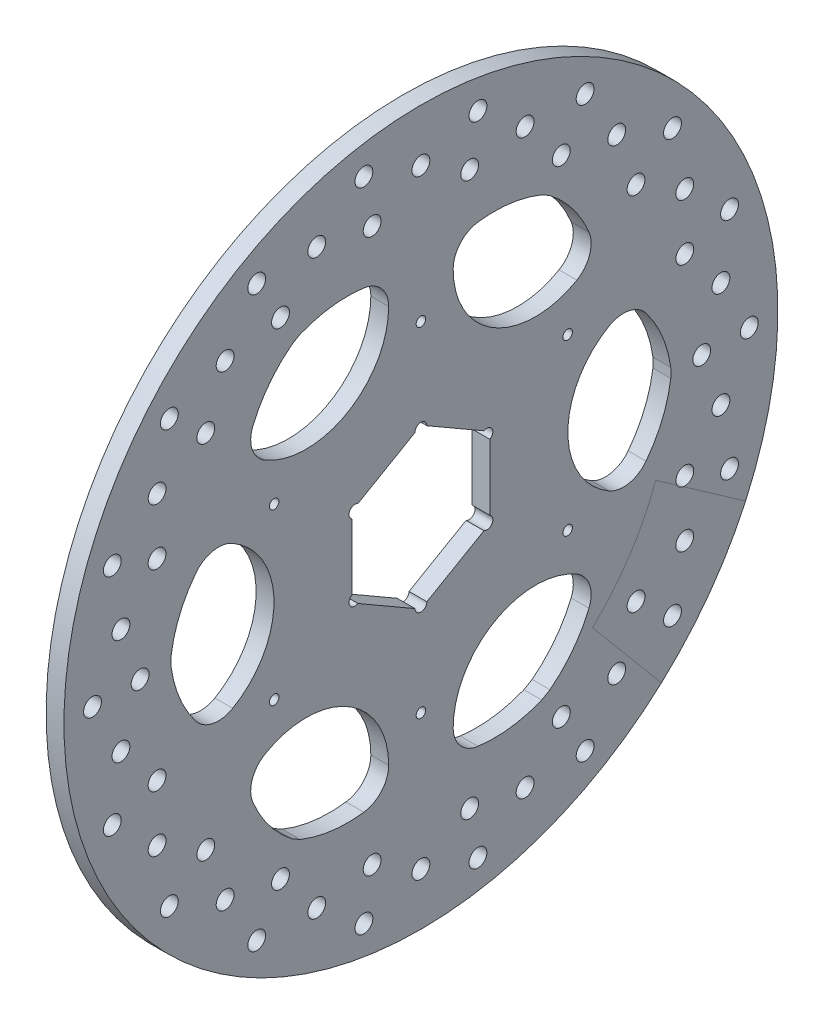
SolidWorks part; units mm, degrees
material "Gray Cast Iron (w/YS)"
ref_plane "X-Y Datum" through (0, 0, 0) normal (0, 0, 1) x (1, 0, 0)
ref_plane "X-Z Datum" through (0, 0, 0) normal (0, 1, 0) x (1, 0, 0)
ref_plane "Y-Z Datum" through (0, 0, 0) normal (1, 0, 0) x (0, 0, -1)
sketch "Sketch1" plane through (0, 0, 0) normal (1, 0, 0) x (0, 0, -1)
  circle A0 centre (0, 0) radius 95.25
  circle A1 centre (0, 0) radius 66.675
  dimension "D1" = 190.5
  dimension "D2" = 133.35
extrude "Main Rotor" add sketch "Sketch1" along normal blind 4.7625
sketch "Sketch2" plane through (4.7625, 0, 0) normal (1, 0, 0) x (0, 0, -1)
  line L0 (0, 0) -> (-50000, 0) construction
  line L1 (0, 0) -> (-93.8029, 16.54) construction
  line L4 (-82.3453, 29.9712) -> (-70.4112, 25.6276) construction
  circle A2 centre (0, 0) radius 95.25 construction
  circle A72 centre (-80.0452, 14.1141) radius 2.3813
  circle A73 centre (0, 0) radius 66.675 construction
  circle A74 centre (-82.3453, 29.9712) radius 2.3812
  circle A75 centre (-70.4112, 25.6276) radius 2.3813
  circle A76 centre (0, 0) radius 95.25 construction
  circle A77 centre (-70.3905, 40.64) radius 2.3812
  circle A78 centre (-67.1285, 56.3275) radius 2.3813
  circle A79 centre (0, 0) radius 66.675 construction
  circle A80 centre (-57.3997, 48.1641) radius 2.3813
  circle A81 centre (-52.2458, 62.2641) radius 2.3813
  circle A82 centre (-87.63, 0) radius 2.3813
  circle A83 centre (-43.815, 75.8898) radius 2.3812
  circle A84 centre (-37.465, 64.8913) radius 2.3813
  circle A85 centre (-74.93, 0) radius 2.3813
  circle A86 centre (-27.7994, 76.3782) radius 2.3812
  circle A87 centre (-15.2168, 86.2987) radius 2.3813
  circle A88 centre (-13.0115, 73.7916) radius 2.3813
  circle A89 centre (0, 81.28) radius 2.3813
  circle A90 centre (15.2168, 86.2987) radius 2.3813
  circle A91 centre (13.0115, 73.7916) radius 2.3813
  circle A92 centre (27.7994, 76.3782) radius 2.3813
  circle A93 centre (43.815, 75.8898) radius 2.3813
  circle A94 centre (37.465, 64.8913) radius 2.3813
  circle A95 centre (52.2458, 62.2641) radius 2.3813
  circle A96 centre (67.1285, 56.3275) radius 2.3813
  circle A97 centre (57.3997, 48.1641) radius 2.3813
  circle A98 centre (70.3905, 40.64) radius 2.3812
  circle A99 centre (82.3453, 29.9712) radius 2.3813
  circle A100 centre (70.4112, 25.6276) radius 2.3813
  circle A101 centre (80.0452, 14.1141) radius 2.3813
  circle A102 centre (87.63, 0) radius 2.3813
  circle A103 centre (74.93, 0) radius 2.3813
  circle A104 centre (80.0452, -14.1141) radius 2.3813
  circle A105 centre (82.3453, -29.9712) radius 2.3812
  circle A106 centre (70.4112, -25.6276) radius 2.3812
  circle A107 centre (70.3905, -40.64) radius 2.3813
  circle A108 centre (67.1285, -56.3275) radius 2.3812
  circle A109 centre (57.3997, -48.1641) radius 2.3813
  circle A110 centre (52.2458, -62.2641) radius 2.3812
  circle A111 centre (43.815, -75.8898) radius 2.3813
  circle A112 centre (37.465, -64.8913) radius 2.3813
  circle A113 centre (27.7994, -76.3782) radius 2.3813
  circle A114 centre (15.2168, -86.2987) radius 2.3813
  circle A115 centre (13.0115, -73.7916) radius 2.3812
  circle A116 centre (0, -81.28) radius 2.3812
  circle A117 centre (-15.2168, -86.2987) radius 2.3813
  circle A118 centre (-13.0115, -73.7916) radius 2.3813
  circle A119 centre (-27.7994, -76.3782) radius 2.3812
  circle A120 centre (-43.815, -75.8898) radius 2.3813
  circle A121 centre (-37.465, -64.8913) radius 2.3813
  circle A122 centre (-52.2458, -62.2641) radius 2.3813
  circle A123 centre (-67.1285, -56.3275) radius 2.3813
  circle A124 centre (-57.3997, -48.1641) radius 2.3813
  circle A125 centre (-70.3905, -40.64) radius 2.3813
  circle A126 centre (-82.3453, -29.9712) radius 2.3813
  circle A127 centre (-70.4112, -25.6276) radius 2.3813
  circle A128 centre (-80.0452, -14.1141) radius 2.3813
  point P109 (0, 0)
  dimension "D1" = 4.7625
  dimension "D2" = 12.7
  dimension "D3" = 10
  dimension "D5" = 81.28
  dimension "D4" = 87.63
  dimension "D6" = 18
extrude "Cut Slots" cut sketch "Sketch2" against normal through all
sketch "Sketch3" plane through (4.7625, 0, 0) normal (1, 0, 0) x (0, 0, -1)
  line L0 (0.3454, 5.0869) -> (-47951.5604, 14168.94) construction
  line L1 (0, 21.2491) -> (-18.4023, 10.6246)
  line L2 (-18.4023, 10.6246) -> (-18.4023, -10.6246)
  line L3 (-18.4023, -10.6246) -> (0, -21.2491)
  line L4 (0, -21.2491) -> (18.4023, -10.6246)
  line L5 (18.4023, -10.6246) -> (18.4023, 10.6246)
  line L6 (18.4023, 10.6246) -> (0, 21.2491)
  line L7 (0, 0) -> (43301.2702, 25000) construction
  line L8 (0, 0) -> (0, 50000) construction
  line L12 (9.525, -59.2994) -> (-9.525, -59.2994) construction
  line L17 (-30.6007, -53.002) -> (24969.3838, 43248.2414) construction
  line L18 (-60.783, 0) -> (49939.217, 0) construction
  line L19 (0, 0) -> (-25000, 43301.2702) construction
  line L20 (-14.2015, 9.3837) -> (0, 17.583) construction
  line L21 (-1.5875, 20.3326) -> (-2.825, 22.476) construction
  arc A0 (8.6043, -53.0208) -> (15.2264, -60.5686) centre (16.2243, -53.0143) ccw
  circle A1 centre (0, 0) radius 66.675 construction
  arc A7 (-15.2264, -60.5686) -> (-32.2316, -58.3668) centre (-19.5921, -27.5182) cw
  arc A10 (15.2264, -60.5686) -> (32.2316, -58.3668) centre (19.5921, -27.5182) ccw
  arc A19 (-19.6024, -33.9524) -> (-8.6043, -53.0208) centre (-30.6006, -53.0019) cw
  arc A25 (41.6152, -33.9619) -> (44.8408, -43.4707) centre (37.7996, -40.5577) cw
  arc A26 (34.4313, -57.0968) -> (66.6629, -1.27) centre (0, 0) ccw
  arc A27 (50.2195, -19.0589) -> (60.0672, -17.0979) centre (54.0238, -12.4565) ccw
  arc A28 (19.6024, -33.9524) -> (8.6043, -53.0208) centre (30.6006, -53.0019) ccw
  arc A29 (60.0672, 17.0979) -> (50.2195, 19.0589) centre (54.0238, 12.4565) ccw
  arc A30 (-44.8408, -43.4707) -> (-34.4313, -57.0968) centre (-14.0354, -30.7264) ccw
  arc A31 (-19.6024, -33.9524) -> (-41.6152, -33.9619) centre (-30.6006, -53.0019) ccw
  arc A32 (-39.2049, 0) -> (-50.2195, -19.0589) centre (-61.2013, 0) cw
  arc A33 (-60.0672, -17.0979) -> (-66.6629, -1.27) centre (-33.6275, 3.2082) cw
  arc A34 (-60.0672, 17.0979) -> (-66.6629, 1.27) centre (-33.6275, -3.2082) ccw
  arc A35 (44.8408, 43.4707) -> (41.6152, 33.9619) centre (37.7996, 40.5577) cw
  arc A36 (-32.2316, -58.3668) -> (32.2316, -58.3668) centre (0, 0) ccw
  arc A37 (15.2264, 60.5686) -> (8.6043, 53.0208) centre (16.2243, 53.0143) ccw
  arc A38 (-8.6043, 53.0208) -> (-15.2264, 60.5686) centre (-16.2243, 53.0143) ccw
  arc A39 (-44.8408, 43.4707) -> (-41.6152, 33.9619) centre (-37.7996, 40.5577) ccw
  arc A40 (-50.2195, 19.0589) -> (-60.0672, 17.0979) centre (-54.0238, 12.4565) ccw
  arc A41 (-50.2195, -19.0589) -> (-60.0672, -17.0979) centre (-54.0238, -12.4565) cw
  arc A42 (-8.6043, -53.0208) -> (-15.2264, -60.5686) centre (-16.2243, -53.0143) cw
  arc A43 (-41.6152, -33.9619) -> (-44.8408, -43.4707) centre (-37.7996, -40.5577) ccw
  arc A44 (-39.2049, 0) -> (-50.2195, 19.0589) centre (-61.2013, 0) ccw
  arc A45 (-19.6025, 33.9524) -> (-41.6152, 33.9619) centre (-30.6007, 53.0019) cw
  arc A46 (-44.8408, 43.4707) -> (-34.4313, 57.0968) centre (-14.0354, 30.7264) cw
  arc A47 (-15.2264, 60.5686) -> (-32.2316, 58.3668) centre (-19.5921, 27.5182) ccw
  arc A48 (-19.6025, 33.9524) -> (-8.6043, 53.0208) centre (-30.6007, 53.0019) ccw
  arc A49 (19.6024, 33.9524) -> (8.6043, 53.0208) centre (30.6006, 53.0019) cw
  arc A50 (15.2264, 60.5686) -> (32.2316, 58.3668) centre (19.5921, 27.5182) cw
  arc A51 (44.8408, 43.4707) -> (34.4313, 57.0968) centre (14.0354, 30.7264) ccw
  arc A52 (19.6024, 33.9524) -> (41.6152, 33.9619) centre (30.6006, 53.0019) ccw
  arc A53 (39.2049, 0) -> (50.2195, 19.0589) centre (61.2013, 0) cw
  arc A54 (60.0672, 17.0979) -> (66.6629, 1.27) centre (33.6275, -3.2082) cw
  arc A55 (60.0672, -17.0979) -> (66.6629, -1.27) centre (33.6275, 3.2082) ccw
  arc A56 (39.2049, 0) -> (50.2195, -19.0589) centre (61.2013, 0) ccw
  arc A57 (19.6024, -33.9524) -> (41.6152, -33.9619) centre (30.6007, -53.0019) cw
  arc A58 (44.8408, -43.4707) -> (34.4313, -57.0968) centre (14.0354, -30.7264) cw
  circle A59 centre (0, 20.3326) radius 1.5875
  arc A60 (-66.6629, -1.27) -> (-34.4313, -57.0968) centre (0, 0) ccw
  arc A62 (-34.4313, 57.0968) -> (-66.6629, 1.27) centre (0, 0) ccw
  arc A64 (32.2316, 58.3668) -> (-32.2316, 58.3668) centre (0, 0) ccw
  arc A66 (66.6629, 1.27) -> (34.4313, 57.0968) centre (0, 0) ccw
  circle A71 centre (0, 0) radius 7.4362 construction
  circle A72 centre (0, 17.583) radius 3.175 construction
  circle A73 centre (17.6086, 10.1663) radius 1.5875
  circle A74 centre (17.6086, -10.1663) radius 1.5875
  circle A75 centre (0, -20.3326) radius 1.5875
  circle A76 centre (-17.6085, -10.1663) radius 1.5875
  circle A77 centre (-17.6085, 10.1663) radius 1.5875
  point P34 (0, -59.2994)
  point P35 (-9.2012, 15.9369)
  point P116 (0, 0)
  point P124 (0, 0)
  dimension "D2" = 42.799
  dimension "D4" = 7.62
  dimension "D7" = 1.27
  dimension "D8" = 33.3375
  dimension "D9" = 21.9964
  dimension "D10" = 3.175
  dimension "D11" = 3.175
  dimension "D12" = 6.35
  dimension "D13" = 6
  dimension "D1" = 36.8046
  dimension "D3" = 6
  dimension "D6" = 19.05
extrude "Boss-Extrude2" add sketch "Sketch3" against normal up to surface (4.7625 mm away) contours A54 A66 A51 A35 A52 A49 A37 A50 A64 A47 A38 A48 A45 A39 A46 A62 A34 A40 A44 A32 A41 A33 A60 A30 A43 A31 A19 A42 A7 A36 A10 A0 A28 A57 A25 A58 A26 A55 A27 A56 A53 A29 L1 A59 L6 L5 L4 region at (4.7625, -59.2833, -9.0788) up to face at (0, 0, 85.2488)
fillet "Fillet1" [suppressed] radius 3.175
sketch "Sketch4" plane through (0, 0, 0) normal (-1, 0, 0) x (0, 0, 1)
  circle A0 centre (0, 45.212) radius 1.27
  circle A1 centre (39.1547, 22.606) radius 1.27
  circle A2 centre (39.1547, -22.606) radius 1.27
  circle A3 centre (0, -45.212) radius 1.27
  circle A4 centre (-39.1547, -22.606) radius 1.27
  circle A5 centre (-39.1547, 22.606) radius 1.27
  point P16 (0, 0)
  dimension "D1" = 45.212
  dimension "D2" = 2.54
  dimension "D3" = 6
extrude "Cut-Extrude2" cut sketch "Sketch4" against normal through all
sketch "Sketch5" plane through (4.7625, 0, 0) normal (1, 0, 0) x (0, 0, -1)
  line L0 (0, 0) -> (-50000, 0) construction
  line L1 (0, 0) -> (-46984.631, 17101.0072) construction
  line L2 (62.654, -22.8042) -> (86.6311, -39.5931)
  line L3 (45.7933, -48.4616) -> (64.1833, -70.378)
  circle A0 centre (0, 0) radius 95.25 construction
  circle A1 centre (0, 0) radius 66.675 construction
  arc A2 (64.1833, -70.378) -> (86.6311, -39.5931) centre (0, 0) ccw
  arc A3 (45.7933, -48.4616) -> (62.654, -22.8042) centre (0, 0) ccw
  dimension "D1" = 20
  dimension "D2" = 15
  dimension "D3" = 15
  dimension "D4" = 38.1
split line "Split Line1"
ref_axis "Axis1" through (5.0006, 0, 0) along (-1, 0, 0)
